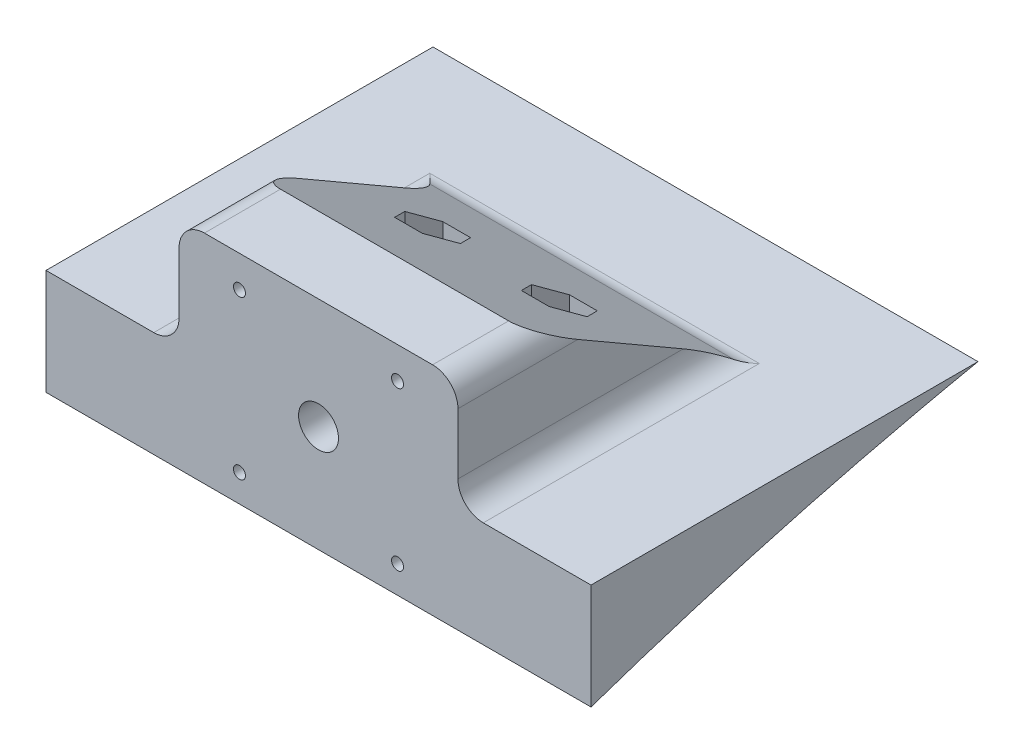
SolidWorks part; units mm, degrees
material "ABS"
ref_plane "Front Plane" through (0, 0, 0) normal (0, 0, 1) x (1, 0, 0)
ref_plane "Top Plane" through (0, 0, 0) normal (0, 1, 0) x (1, 0, 0)
ref_plane "Right Plane" through (0, 0, 0) normal (1, 0, 0) x (0, 0, -1)
curve "Curve1"
  spline degree 3 poles (0, 0.0012, 1.0003) (0, 0.0015, 0.9994) (0, 0.0028, 0.9958) (0, 0.0055, 0.9879) (0, 0.0099, 0.9747) (0, 0.0159, 0.9565) (0, 0.0233, 0.9333) (0, 0.0318, 0.9054) (0, 0.0411, 0.8731) (0, 0.051, 0.8366) (0, 0.0612, 0.7964) (0, 0.0713, 0.7528) (0, 0.0811, 0.7063) (0, 0.0903, 0.6574) (0, 0.0985, 0.6067) (0, 0.1057, 0.5546) (0, 0.1115, 0.5018) (0, 0.1158, 0.4488) (0, 0.1186, 0.3959) (0, 0.1189, 0.3436) (0, 0.1164, 0.2927) (0, 0.1112, 0.2442) (0, 0.1037, 0.1988) (0, 0.0942, 0.157) (0, 0.0831, 0.1194) (0, 0.0711, 0.0865) (0, 0.0584, 0.0585) (0, 0.0457, 0.0357) (0, 0.0334, 0.0184) (0, 0.0218, 0.0064) (0, 0.0108, -0.0005) (0, -0.0003, -0.0011) (0, -0.0092, 0.0055) (0, -0.0148, 0.017) (0, -0.0185, 0.0329) (0, -0.0204, 0.0533) (0, -0.0208, 0.0781) (0, -0.0198, 0.107) (0, -0.0176, 0.1398) (0, -0.0147, 0.176) (0, -0.0111, 0.2153) (0, -0.0074, 0.2574) (0, -0.0037, 0.3019) (0, -0.0005, 0.3484) (0, 0.002, 0.397) (0, 0.0037, 0.4471) (0, 0.0055, 0.4983) (0, 0.0069, 0.5496) (0, 0.0079, 0.6006) (0, 0.0085, 0.6505) (0, 0.0086, 0.699) (0, 0.0083, 0.7455) (0, 0.0076, 0.7894) (0, 0.0065, 0.8302) (0, 0.0053, 0.8675) (0, 0.0039, 0.9007) (0, 0.0027, 0.9296) (0, 0.0013, 0.9539) (0, 0.0006, 0.9727) (0, -0.0011, 0.9872) (0, 0, 0.9944) (0, -0.002, 0.9999) (0, -0.0005, 1) (0, 0, 1) knots 0 0 0 0 0.001372 0.005465 0.012235 0.021602 0.033461 0.047671 0.064081 0.082496 0.102719 0.124527 0.147676 0.171913 0.196978 0.222597 0.248497 0.274385 0.300041 0.32569 0.350525 0.37428 0.396711 0.417577 0.436654 0.453744 0.46868 0.481329 0.491631 0.499616 0.505546 0.510185 0.514824 0.520702 0.528516 0.538466 0.550543 0.564643 0.580638 0.598345 0.617584 0.638174 0.659922 0.682632 0.706121 0.730727 0.7557 0.780732 0.805564 0.829932 0.85357 0.876213 0.89761 0.917519 0.935698 0.951943 0.966047 0.97784 0.987174 0.993932 0.998018 0.999386 1 1 1 1
sketch "Sketch1" plane through (0, 0, 0) normal (1, 0, 0) x (0, 0, -1)
  line L3 (195.725, 0) -> (-195.725, 0) construction
  line L4 (71.5374, 26.4626) -> (-25.4, 26.4626)
  line L5 (-25.4, 26.4626) -> (-25.4, 0)
  spline S1 degree 3 poles (-25.4, 0) (-25.0834, 0.108) (-23.8218, 0.5382) (-20.9978, 1.5029) (-16.3151, 3.0589) (-6.5282, 6.2519) (9.8573, 11.2778) (28.9301, 16.5496) (47.1199, 21.0862) (60.1793, 24.0716) (68.4583, 25.8283) (71.5374, 26.4626) knots 0 0 0 0 0.001372 0.005465 0.012235 0.021602 0.047671 0.082496 0.102719 0.124527 0.137416 0.137416 0.137416 0.137416
  dimension "D1" = 26.4626
  dimension "D2" = 25.4
  dimension "D3" = 96.9374
extrude "Boss-Extrude1" add sketch "Sketch1" along normal mid plane 136.525
sketch "Sketch4" plane through (0, 0, 25.4) normal (0, 0, 1) x (1, 0, 0)
  line L0 (68.2625, 26.4626) -> (-68.2625, 26.4626) construction
  line L1 (-34.925, 54.4026) -> (34.925, 54.4026)
  line L2 (-34.925, 54.4026) -> (-34.925, 26.4626)
  line L3 (-34.925, 26.4626) -> (34.925, 26.4626)
  line L4 (34.925, 54.4026) -> (34.925, 26.4626)
  point P6 (0, 26.4626)
  dimension "D1" = 27.94
  dimension "D2" = 69.85
extrude "Boss-Extrude2" add sketch "Sketch4" against normal blind 50.8
sketch "Sketch2" plane through (0, 26.4626, 0) normal (0, 1, 0) x (1, 0, 0)
  line L0 (-68.2625, 19.05) -> (68.2625, 19.05) construction
  line L1 (-68.2625, 71.5374) -> (-68.2625, -25.4) construction
  line L2 (68.2625, 71.5374) -> (68.2625, -25.4) construction
  line L3 (-15.875, 19.05) -> (-15.875, 71.5374) construction
  line L4 (68.2625, 71.5374) -> (-68.2625, 71.5374) construction
  line L5 (15.875, 19.05) -> (15.875, 71.5374) construction
  line L6 (-68.2625, -286.8403) -> (-15.875, -286.8403) construction
  line L7 (-15.875, -286.8403) -> (15.875, -286.8403) construction
  line L8 (15.875, -286.8403) -> (68.2625, -286.8403) construction
  line L9 (-34.925, -25.4) -> (-68.2625, -25.4) construction
  circle A0 centre (-15.875, 19.05) radius 3.4925
  circle A1 centre (15.875, 19.05) radius 3.4925
  dimension "D1" = 6.985
  dimension "D2" = 6.985
  dimension "D3" = 31.75
  dimension "D4" = 44.45
extrude "Cut-Extrude1" cut sketch "Sketch2" against normal through all and the other way through all
sketch "Sketch5" plane through (0, 0, 25.4) normal (0, 0, 1) x (1, 0, 0)
  line L0 (68.2625, 0) -> (-68.2625, 0) construction
  circle A0 centre (0, 26.67) radius 5
  dimension "D1" = 10
  dimension "D2" = 26.67
extrude "Cut-Extrude2" cut sketch "Sketch5" against normal blind 12.7
sketch "Sketch6" plane through (0, 0, 25.4) normal (0, 0, 1) x (1, 0, 0)
  line L0 (0, 26.67) -> (26.9784, 53.6484) construction
  line L1 (0, 26.67) -> (45.1172, 26.67) construction
  circle A0 centre (19.799, 46.469) radius 1.5
  dimension "D1" = 3
  dimension "D2" = 28
  dimension "D3" = 45
extrude "Cut-Extrude3" cut sketch "Sketch6" against normal blind 6.35
pattern_circular "CirPattern1" count 4 over 360 about axis through (0, 26.67, 12.7) along (0, 0, 1) of "Cut-Extrude3"
sketch "Sketch7" plane through (-34.925, 0, 0) normal (-1, 0, 0) x (0, 0, 1)
  line L0 (-25.4, 54.4026) -> (-71.5374, 26.4626)
  line L1 (-71.5374, 26.4626) -> (25.4, 26.4626) construction
  line L2 (-71.5374, 26.4626) -> (-25.4, 26.4626)
  line L3 (-25.4, 26.4626) -> (-25.4, 54.4026)
  spline S0 degree 3 poles (25.4, 0) (25.0834, 0.108) (23.8218, 0.5382) (20.9978, 1.5029) (16.3151, 3.0589) (6.5282, 6.2519) (-9.8573, 11.2778) (-28.9301, 16.5496) (-47.1199, 21.0862) (-60.1793, 24.0716) (-68.4583, 25.8283) (-71.5374, 26.4626) knots 0 0 0 0 0.001372 0.005465 0.012235 0.021602 0.047671 0.082496 0.102719 0.124527 0.137416 0.137416 0.137416 0.137416 construction
extrude "Boss-Extrude3" add sketch "Sketch7" against normal up to surface (69.85 mm away) up to face at (34.925, 40.4326, 0)
sketch "Sketch8" plane through (0, 54.4026, 0) normal (0, 1, 0) x (1, 0, 0)
  circle A0 centre (15.875, 19.05) radius 6.35
  circle A1 centre (-15.875, 19.05) radius 6.35
  dimension "D1" = 12.7
extrude "Cut-Extrude4" cut sketch "Sketch8" against normal blind 6.35
sketch "Sketch9" plane through (-34.925, 0, 0) normal (-1, 0, 0) x (0, 0, 1)
  line L1 (-71.5374, 26.4626) -> (-42.0435, 26.4626)
  line L2 (-71.5374, 26.4626) -> (-71.5374, 54.4026)
  line L3 (-71.5374, 54.4026) -> (6.35, 54.4026)
  line L5 (-25.4, 54.4026) -> (25.4, 54.4026) construction
  line L6 (-42.0435, 26.4626) -> (6.35, 54.4026)
  line L7 (25.4, 54.4026) -> (25.4, 26.4626) construction
  dimension "D1" = 19.05
  dimension "D2" = 30
extrude "Cut-Extrude5" cut sketch "Sketch9" against normal through all both and the other way through all
sketch "Sketch10" plane through (0, 54.4026, 0) normal (0, 1, 0) x (1, 0, 0)
  line L1 (22.8407, 19.05) -> (19.3579, 25.0825)
  line L2 (19.3579, 25.0825) -> (12.3921, 25.0825)
  line L3 (12.3921, 25.0825) -> (8.9093, 19.05)
  line L4 (8.9093, 19.05) -> (12.3921, 13.0175)
  line L5 (12.3921, 13.0175) -> (19.3579, 13.0175)
  line L6 (19.3579, 13.0175) -> (22.8407, 19.05)
  line L7 (-8.9093, 19.05) -> (-12.3921, 25.0825)
  line L8 (-12.3921, 25.0825) -> (-19.3579, 25.0825)
  line L9 (-19.3579, 25.0825) -> (-22.8407, 19.05)
  line L10 (-22.8407, 19.05) -> (-19.3579, 13.0175)
  line L11 (-19.3579, 13.0175) -> (-12.3921, 13.0175)
  line L12 (-12.3921, 13.0175) -> (-8.9093, 19.05)
  circle A2 centre (15.875, 19.05) radius 6.0325 construction
  circle A3 centre (-15.875, 19.05) radius 6.0325 construction
  dimension "D1" = 12.065
  dimension "D2" = 12.065
extrude "Cut-Extrude6" cut sketch "Sketch10" against normal blind 29.21
fillet "Fillet1" radius 6.35 3 edges at (-34.925, 26.4626, -8.3217) (34.925, 26.4626, -8.3217) (0, 26.4626, -42.0435)
fillet "Fillet2" radius 6.35 2 edges at (-34.925, 54.4026, 15.875) (34.925, 54.4026, 15.875)
